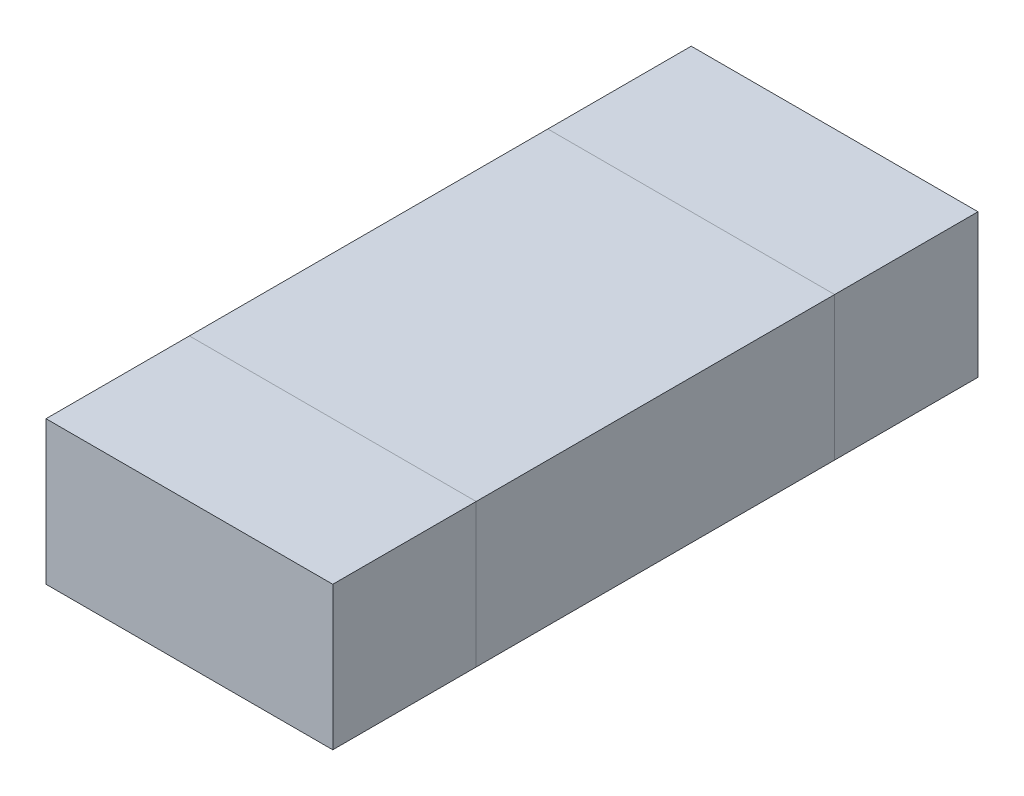
SolidWorks part; units mm, degrees
ref_plane "Front Plane" through (0, 0, 0) normal (0, 0, 1) x (1, 0, 0)
ref_plane "Top Plane" through (0, 0, 0) normal (0, 1, 0) x (1, 0, 0)
ref_plane "Right Plane" through (0, 0, 0) normal (1, 0, 0) x (0, 0, -1)
sketch "MainBodyS" plane through (0, 0, 0) normal (0, 1, 0) x (1, 0, 0)
  line L1 (-0.4, 0.5) -> (0.4, 0.5)
  line L2 (-0.4, 0.5) -> (-0.4, -0.5)
  line L3 (-0.4, -0.5) -> (0.4, -0.5)
  line L4 (0.4, 0.5) -> (0.4, -0.5)
  line L5 (-0.4, 0.5) -> (0.4, -0.5) construction
  line L6 (-0.4, -0.5) -> (0.4, 0.5) construction
  point P0 (0, 0)
  dimension "Length" = 1
  dimension "Width" = 0.8
extrude "MainBody" add sketch "MainBodyS" along normal blind 0.4
sketch "LeftBodyS" plane through (0, 0, 0) normal (0, -1, 0) x (-1, 0, 0)
  line L1 (0.4, -0.5) -> (-0.4, -0.5)
  line L2 (0.4, -0.5) -> (0.4, -0.9)
  line L3 (0.4, -0.9) -> (-0.4, -0.9)
  line L4 (-0.4, -0.5) -> (-0.4, -0.9)
  dimension "Width" = 0.4
extrude "Boss-Extrude1" add sketch "LeftBodyS" against normal up to surface (0.4 mm away) separate body up to face at (0, 0.4, 0)
sketch "RightBodyS" plane through (0, 0, 0) normal (0, -1, 0) x (1, 0, 0)
  line L0 (0.4, 0.5) -> (0.4, 0.9) construction
  line L1 (-0.4, -0.5) -> (0.4, -0.5)
  line L2 (-0.4, -0.5) -> (-0.4, -0.9)
  line L3 (-0.4, -0.9) -> (0.4, -0.9)
  line L4 (0.4, -0.5) -> (0.4, -0.9)
extrude "Boss-Extrude2" add sketch "RightBodyS" against normal up to surface (0.4 mm away) separate body up to face at (0, 0.4, 0)
